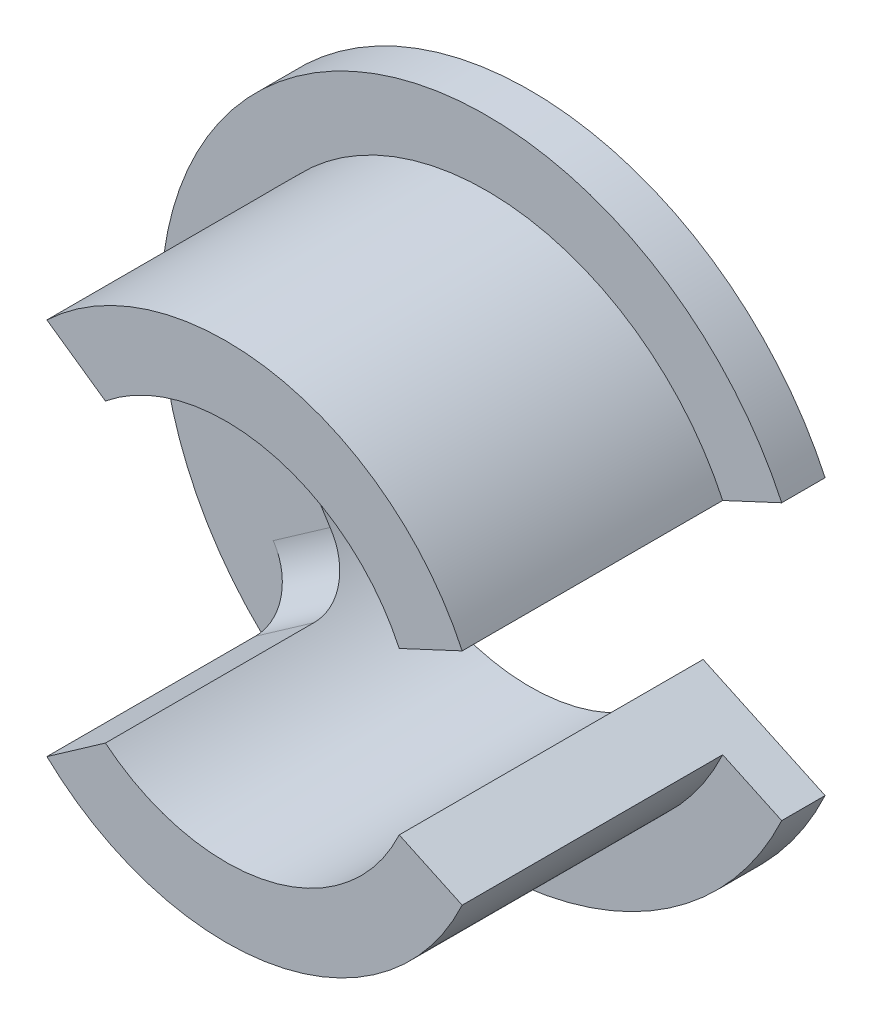
SolidWorks part; units mm, degrees
ref_plane "Front Plane" through (0, 0, 0) normal (0, 0, 1) x (1, 0, 0)
ref_plane "Top Plane" through (0, 0, 0) normal (0, 1, 0) x (1, 0, 0)
ref_plane "Right Plane" through (0, 0, 0) normal (1, 0, 0) x (0, 0, -1)
sketch "Sketch1" plane through (0, 0, 0) normal (0, 0, 1) x (1, 0, 0)
  line L0 (3.9878, 1.8595) -> (5.4378, 2.5357)
  line L1 (5.4378, -2.5357) -> (3.9878, -1.8595)
  line L2 (-3.9, 0) -> (-4.4, 0) construction
  line L3 (-6, 0) -> (-6.5, 0) construction
  circle A0 centre (0, 0) radius 3.9 construction
  arc A1 (0, 6.5) -> (0, -6.5) centre (0, 0) ccw construction
  arc A2 (5.4378, 2.5357) -> (5.4378, -2.5357) centre (0, 0) ccw
  arc A3 (3.9878, -1.8595) -> (3.9878, 1.8595) centre (0, 0) cw
  dimension "D1" = 7.8
  dimension "D2" = 6.5
  dimension "D3" = 1.6
  dimension "D4" = 50
extrude "Boss-Extrude1" add sketch "Sketch1" along normal blind 6
sketch "Sketch2" plane through (0, 0, 0) normal (0, 0, -1) x (-1, 0, 0)
  line L0 (-3.9878, 1.8595) -> (-5.4378, 2.5357) construction
  line L1 (-3.9878, 1.8595) -> (-5.4378, 2.5357)
  line L2 (-5.4378, -2.5357) -> (-3.9878, -1.8595) construction
  line L3 (-5.4378, -2.5357) -> (-3.9878, -1.8595)
  line L4 (-5.4378, 2.5357) -> (-6.7973, 3.1696)
  line L5 (-5.4378, -2.5357) -> (-6.7973, -3.1696)
  circle A0 centre (0, 0) radius 7.5
  circle A1 centre (0, 0) radius 4.4
  arc M1 (-5.4378, -2.5357) -> (-5.4378, 2.5357) centre (0, 0) ccw
  line M2 (-5.4378, 2.5357) -> (-3.9878, 1.8595)
  arc M3 (-3.9878, 1.8595) -> (-3.9878, -1.8595) centre (0, 0) cw
  line M4 (-3.9878, -1.8595) -> (-5.4378, -2.5357)
  dimension "D1" = 15
  dimension "D2" = 8.8
extrude "Boss-Extrude2" add sketch "Sketch2" along normal blind 1 contours M4 M1 M2 M3 | L5 A0 L4 M1 region at (4.6427, 2.3479, 0) region at (6.03, 3.0405, 0)
sketch "Sketch3" plane through (0, 0, 6) normal (0, 0, 1) x (1, 0, 0)
  line L0 (0, 0) -> (-14.0798, 0) construction
  line L1 (-5.3762, -5.2294) -> (-2.7793, -3.411)
  line L2 (-6.7528, -3.2634) -> (-4.1559, -1.4451)
  line L3 (0, 0) -> (-11.4084, -7.9882) construction
  line L4 (-4.0778, -4.3202) -> (-5.4544, -2.3543) construction
  line L5 (0, 0) -> (-11.4084, 7.9882) construction
  line L6 (-4.0778, 4.3202) -> (-5.4544, 2.3543) construction
  line L7 (-6.7528, 3.2634) -> (-4.1559, 1.4451)
  line L8 (-5.3762, 5.2294) -> (-2.7793, 3.411)
  arc A0 (6.7973, 3.1696) -> (6.7973, -3.1696) centre (0, 0) ccw construction
  arc A1 (3.9878, 1.8595) -> (3.9878, -1.8595) centre (0, 0) ccw construction
  arc A2 (6.7973, 3.1696) -> (6.7973, -3.1696) centre (0, 0) ccw
  arc A3 (3.9878, 1.8595) -> (3.9878, -1.8595) centre (0, 0) ccw
  arc M7 (5.4378, 2.5357) -> (5.4378, -2.5357) centre (0, 0) ccw
  arc M9 (3.9878, -1.8595) -> (3.9878, 1.8595) centre (0, 0) cw
  dimension "D1" = 2.4
  dimension "D2" = 70
extrude "Cut-Extrude1" cut sketch "Sketch3" against normal blind 6 contours L2 L1 M7 M9 | L8 A2 L7 M7 | L8 L7 M7 M9 | L2 A2 L1 M7 region at (-5.4995, -3.8508, 6) region at (-4.2202, -2.955, 6) region at (-5.4995, 3.8508, 6) region at (-4.2202, 2.955, 6)
sketch "Sketch4" plane through (0, 0, 6) normal (0, 0, 1) x (1, 0, 0)
  line L2 (-4.1559, 1.4451) -> (-5.5039, 2.3889)
  line L3 (-5.5039, -2.3889) -> (-4.1559, -1.4451)
  line L4 (-4.1559, 1.4451) -> (-5.5039, 2.3889)
  line L5 (-5.5039, -2.3889) -> (-4.1559, -1.4451)
  arc A2 (-5.5039, 2.3889) -> (-5.5039, -2.3889) centre (0, 0) ccw
  arc A3 (-4.1559, 1.4451) -> (-4.1559, -1.4451) centre (0, 0) ccw
  arc A4 (-5.5039, 2.3889) -> (-5.5039, -2.3889) centre (0, 0) ccw
  arc A5 (-4.1559, 1.4451) -> (-4.1559, -1.4451) centre (0, 0) ccw
  dimension "D1" = 0
extrude "Cut-Extrude2" cut sketch "Sketch4" against normal up to surface (6 mm away) up to face at (-1.8998, 0, 0)
fillet "Fillet1" radius 1.2 2 edges at (-3.4533, -3.883, 0) (-3.4533, 3.883, 0)
